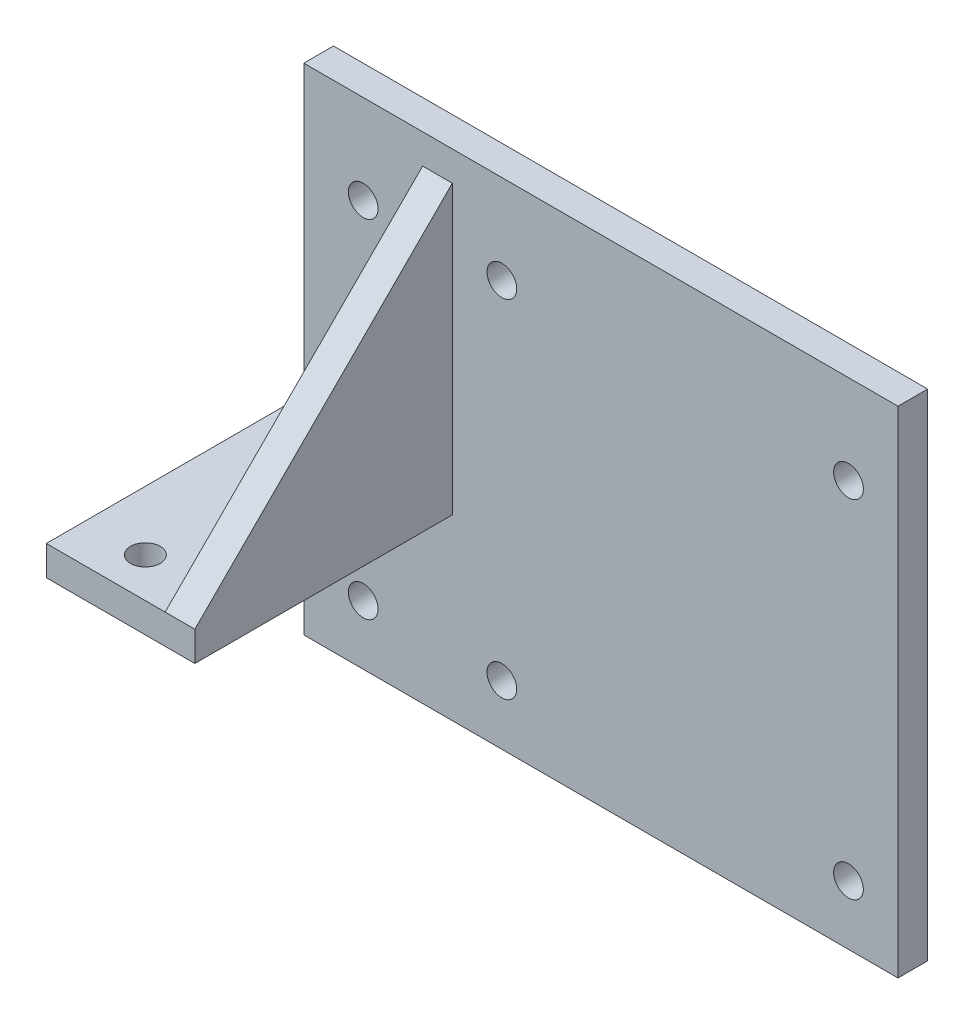
SolidWorks part; units mm, degrees
ref_plane "Front Plane" through (0, 0, 0) normal (0, 0, 1) x (1, 0, 0)
ref_plane "Top Plane" through (0, 0, 0) normal (0, 1, 0) x (1, 0, 0)
ref_plane "Right Plane" through (0, 0, 0) normal (1, 0, 0) x (0, 0, -1)
sketch "Sketch1" plane through (0, 0, 0) normal (0, 0, 1) x (1, 0, 0)
  line L1 (0, 0) -> (60, 0)
  line L2 (0, 0) -> (0, 50)
  line L3 (0, 50) -> (60, 50)
  line L4 (60, 0) -> (60, 50)
  dimension "D1" = 60
  dimension "D2" = 50
extrude "Boss-Extrude1" add sketch "Sketch1" along normal blind 3
sketch "Sketch2" plane through (0, 0, 3) normal (0, 0, 1) x (1, 0, 0)
  line L0 (6, -4.5714) -> (6, 59.5728) construction
  line L1 (20, 6) -> (55, 6) construction
  line L2 (20, 6) -> (20, 41) construction
  line L3 (20, 41) -> (55, 41) construction
  line L4 (55, 6) -> (55, 41) construction
  circle A3 centre (20, 6) radius 1.5
  circle A4 centre (20, 41) radius 1.5
  circle A5 centre (55, 41) radius 1.5
  circle A6 centre (55, 6) radius 1.5
  circle A7 centre (6, 6) radius 1.5
  circle A8 centre (6, 41) radius 1.5
  dimension "D1" = 3
  dimension "D8" = 3
  dimension "D2" = 35
  dimension "D3" = 35
  dimension "D4" = 14
  dimension "D5" = 6
  dimension "D6" = 35
  dimension "D7" = 6
  dimension "D9" = 6
extrude "Cut-Extrude1" cut sketch "Sketch2" against normal through all
sketch "Sketch3" plane through (0, 0, 3) normal (0, 0, 1) x (1, 0, 0)
  line L0 (0, 50) -> (0, 0) construction
  line L1 (0, 18) -> (12, 18)
  line L2 (0, 18) -> (0, 21)
  line L3 (0, 21) -> (12, 21)
  line L4 (12, 18) -> (12, 21)
  dimension "D1" = 3
  dimension "D2" = 12
  dimension "D3" = 18
extrude "Boss-Extrude2" add sketch "Sketch3" along normal blind 26
sketch "Sketch5" plane through (0, 21, 0) normal (0, 1, 0) x (1, 0, 0)
  line L0 (6, -29.5175) -> (6, 3.8156) construction
  line L1 (0, -29) -> (0, -3) construction
  line L5 (60, -3) -> (0, -3) construction
  circle A0 centre (6, -7) radius 1.5
  circle A1 centre (6, -25) radius 1.5
  dimension "D2" = 3
  dimension "D1" = 6
  dimension "D3" = 18
  dimension "D4" = 4
extrude "Cut-Extrude2" cut sketch "Sketch5" against normal blind 10
sketch "Sketch6" plane through (12, 0, 0) normal (1, 0, 0) x (0, 0, -1)
  line L0 (-3, 18) -> (-29, 18)
  line L1 (-29, 18) -> (-29, 21)
  line L2 (-29, 21) -> (-3, 47)
  line L3 (-3, 47) -> (-3, 18)
  line L4 (-29, 21) -> (-3, 21) construction
  dimension "D1" = 45
extrude "Boss-Extrude3" add sketch "Sketch6" along normal blind 3
